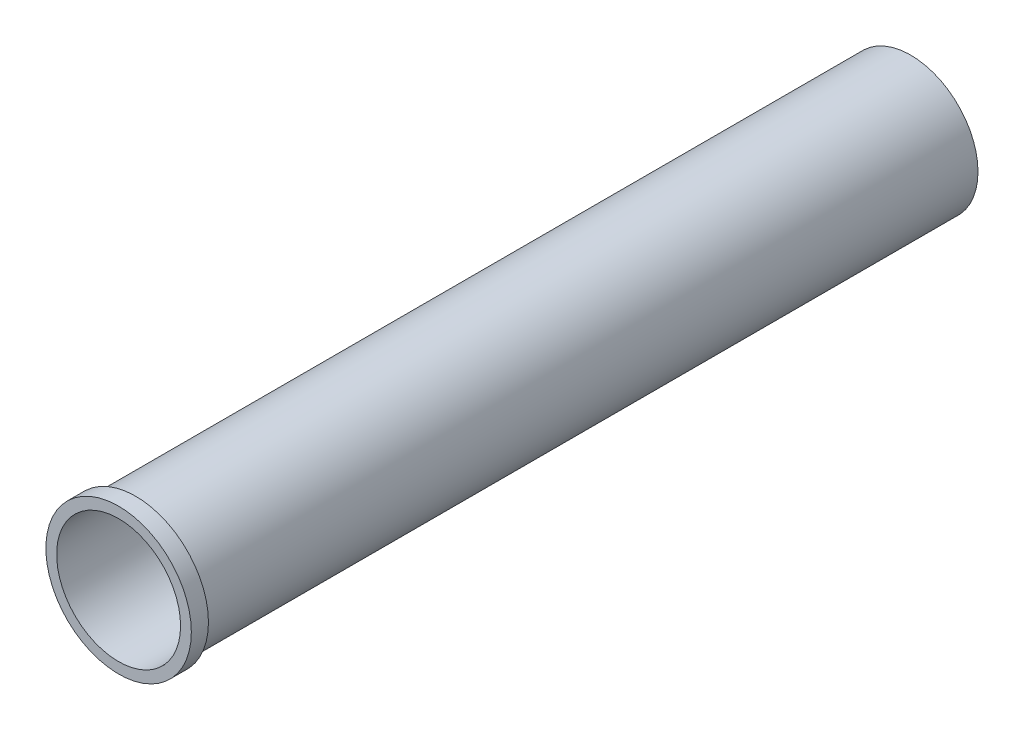
SolidWorks part; units mm, degrees
material "6061-T6 (SS)"
ref_plane "Front Plane" through (0, 0, 0) normal (0, 0, 1) x (1, 0, 0)
ref_plane "Top Plane" through (0, 0, 0) normal (0, 1, 0) x (1, 0, 0)
ref_plane "Right Plane" through (0, 0, 0) normal (1, 0, 0) x (0, 0, -1)
ref_axis "Axis X" through (-88.99, 0, 0) along (1, 0, 0)
ref_axis "Axis Y" through (0, 55, 0) along (0, -1, 0)
ref_axis "Axis Z" through (0, 0, -88.99) along (0, 0, 1)
sketch "Sketch1" plane through (0, 0, 0) normal (0, 0, 1) x (1, 0, 0)
  circle A0 centre (0, 0) radius 23
  circle A1 centre (0, 0) radius 25
  dimension "D1" = 46
  dimension "D2" = 50
extrude "Boss-Extrude1" add sketch "Sketch1" along normal mid plane 294
sketch "Sketch2" plane through (0, 0, 147) normal (0, 0, 1) x (1, 0, 0)
  circle A0 centre (0, 0) radius 25
  circle A1 centre (0, 0) radius 27
  circle A2 centre (0, 0) radius 25 construction
  dimension "D1" = 2
extrude "Boss-Extrude2" add sketch "Sketch2" against normal blind 6.35
